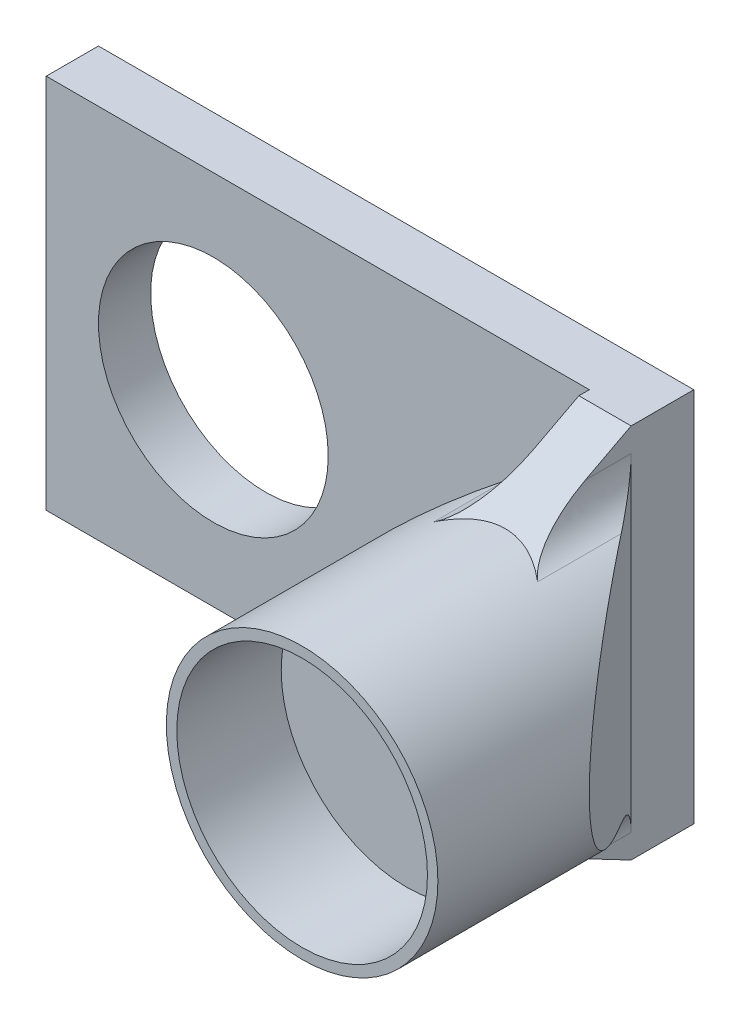
SolidWorks part; units mm, degrees
material "201 Stal nierdzewna odprężona (SS)"
ref_plane "Płaszczyzna przednia" through (0, 0, 0) normal (0, 0, 1) x (1, 0, 0)
ref_plane "Płaszczyzna górna" through (0, 0, 0) normal (0, 1, 0) x (1, 0, 0)
ref_plane "Płaszczyzna prawa" through (0, 0, 0) normal (1, 0, 0) x (0, 0, -1)
sketch "Szkic1" plane through (0, 0, 0) normal (0, 0, 1) x (1, 0, 0)
  line L1 (0, 0) -> (18, 0)
  line L2 (0, 0) -> (0, -18)
  line L3 (0, -18) -> (18, -18)
  line L4 (18, 0) -> (18, -18)
  dimension "D1" = 18
  dimension "D2" = 18
extrude "Dodanie-wyciągnięcie1" add sketch "Szkic1" along normal blind 2.5
ref_plane "Płaszczyzna1" through (0, 0, 12.5) normal (0, 0, 1) x (1, 0, 0)
sketch "Szkic3" plane through (0, 0, 12.5) normal (0, 0, 1) x (1, 0, 0)
  circle A0 centre (19.25, -9) radius 6.5
  circle A1 centre (19.25, -9) radius 6
extrude "Dodanie-wyciągnięcie2" add sketch "Szkic3" along normal blind 5 separate body
sketch "Szkic5" plane through (0, 0, 12.5) normal (0, 0, 1) x (1, 0, 0)
  circle A1 centre (19.25, -9) radius 6.5
extrude "Dodanie-wyciągnięcie3" add sketch "Szkic5" against normal blind 9.5
ref_plane "Płaszczyzna2" through (0, 0, 0) normal (0, 0, -1) x (-1, 0, 0)
sketch "Szkic6" plane through (0, 0, 0) normal (0, 0, -1) x (-1, 0, 0)
  line L1 (-18, -18) -> (-20.5, -18)
  line L2 (-18, -18) -> (-18, 0)
  line L3 (-18, 0) -> (-20.5, 0)
  line L4 (-20.5, -18) -> (-20.5, 0)
extrude "Dodanie-wyciągnięcie4" add sketch "Szkic6" against normal blind 3
ref_plane "Płaszczyzna4" through (0, 0, 0) normal (0, 1, 0) x (1, 0, 0)
sketch "Szkic17" plane through (0, 0, 0) normal (0, 1, 0) x (1, 0, 0)
  line L0 (20.5, -3) -> (25.75, -10.25)
  line L1 (25.75, -17.5) -> (25.75, -3) construction
  line L2 (25.75, -10.25) -> (25.75, -3)
  line L3 (25.75, -3) -> (20.5, -3)
  line L4 (18, -3) -> (12.6968, -12.75)
  line L5 (12.6968, -12.75) -> (12.75, -3)
  line L6 (12.75, -3) -> (18, -3)
extrude "Wytnij-wyciągnięcie3" cut sketch "Szkic17" against normal blind 20
ref_plane "Płaszczyzna5" through (20.5, 0, 0) normal (1, 0, 0) x (0, 0, -1)
sketch "Szkic19" plane through (20.5, 0, 0) normal (1, 0, 0) x (0, 0, -1)
  line L0 (-3, -18) -> (-3, -15.3787)
  line L1 (-3, -15.3787) -> (-8, -15.3787)
  line L2 (-8, -15.3787) -> (-3, -18)
  line L3 (-3, 0) -> (-3, -2.6213)
  line L4 (-3, -2.6213) -> (-8, -2.6213)
  line L5 (-8, -2.6213) -> (-3, 0)
extrude "Dodanie-wyciągnięcie11" add sketch "Szkic19" against normal blind 2.5
fillet "Zaokrąglenie3" radius 2 2 edges at (20.5, -15.3787, 5.5) (25.75, -9, 10.25)
fillet "Zaokrąglenie4" radius 2 1 edges at (20.5, -2.6213, 5.5)
fillet "Zaokrąglenie5" radius 2 1 edges at (18, -15.3787, 5.5)
fillet "Zaokrąglenie6" radius 2 2 edges at (12.7821, -8.3549, 12.5933) (18, -2.6213, 5.5)
sketch "Szkic21" plane through (0, 0, 0) normal (-1, 0, 0) x (0, 0, 1)
  line L1 (2.5, 0) -> (0, 0)
  line L2 (2.5, 0) -> (2.5, -18)
  line L3 (2.5, -18) -> (0, -18)
  line L4 (0, 0) -> (0, -18)
extrude "Dodanie-wyciągnięcie12" add sketch "Szkic21" along normal blind 8
sketch "Szkic23" plane through (0, 0, 2.5) normal (0, 0, 1) x (1, 0, 0)
  circle A2 centre (0, -9) radius 5.5
  dimension "D1" = 11
extrude "Wytnij-wyciągnięcie4" cut sketch "Szkic23" against normal blind 2.5
